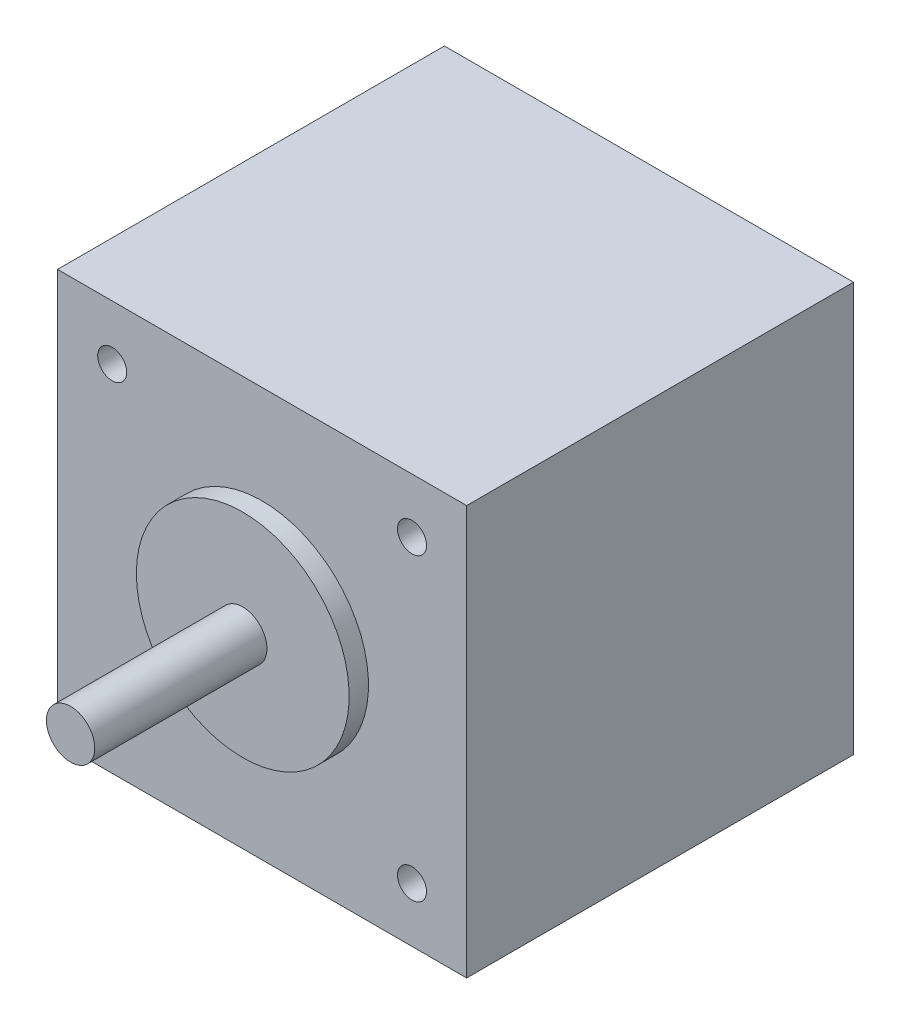
SolidWorks part; units mm, degrees
ref_plane "Спереди" through (0, 0, 0) normal (0, 0, 1) x (1, 0, 0)
ref_plane "Сверху" through (0, 0, 0) normal (0, 1, 0) x (1, 0, 0)
ref_plane "Справа" through (0, 0, 0) normal (1, 0, 0) x (0, 0, -1)
other "Configuration Table"
sketch "Эскиз1" plane through (0, 0, 0) normal (0, 0, 1) x (1, 0, 0)
  line L1 (-21.15, -21.15) -> (21.15, -21.15)
  line L2 (-21.15, -21.15) -> (-21.15, 21.15)
  line L3 (-21.15, 21.15) -> (21.15, 21.15)
  line L4 (21.15, -21.15) -> (21.15, 21.15)
  line L5 (-21.15, -21.15) -> (21.15, 21.15) construction
  line L6 (-21.15, 21.15) -> (21.15, -21.15) construction
  point P0 (0, 0)
  dimension "D1" = 42.3
  dimension "D2" = 42.3
extrude "Корпус" add sketch "Эскиз1" along normal blind 40
sketch "Эскиз2" plane through (0, 0, 0) normal (0, 0, 1) x (1, 0, 0)
  circle A0 centre (0, 0) radius 2.5
extrude "Вал_ПРЕДВ" add sketch "Эскиз2" along normal blind 59.8
sketch "Эскиз3" plane through (0, 0, 0) normal (0, 0, 1) x (1, 0, 0)
  circle A0 centre (0, 0) radius 11
  dimension "D1" = 22
extrude "Буртик_ПРЕДВ" add sketch "Эскиз3" along normal blind 42
sketch "Эскиз4" plane through (0, 0, 0) normal (0, 0, 1) x (1, 0, 0)
  circle A0 centre (0, 0) radius 8
  dimension "D1" = 16
sketch "Эскиз5" plane through (0, 0, 0) normal (0, 0, 1) x (1, 0, 0)
  circle A0 centre (-15.5, -15.5) radius 1.5
  circle A1 centre (-15.5, 15.5) radius 1.5
  circle A2 centre (15.5, -15.5) radius 1.5
  circle A3 centre (15.5, 15.5) radius 1.5
  dimension "D1" = 3
  dimension "D2" = 3
  dimension "D3" = 3
  dimension "D4" = 3
extrude "Крепеж_М3_ПРЕДВ" cut sketch "Эскиз5" against normal blind 4.5 from offset 40
equation "\"Мотор X ширина корпуса\"= 42.3"
equation "\"Мотор X высота корпуса\"= 42.3"
equation "\"Мотор X длина корпуса\"= 40"
equation "\"Мотор X вылет вала\"= 19.8"
equation "\"Мотор Y ширина корпуса\"= 42.3"
equation "\"Мотор Y высота корпуса\"= 42.3"
equation "\"Мотор Y длина корпуса\"= 48"
equation "\"Мотор Y вылет вала\"= 30"
equation "\"Мотор Z ширина корпуса\"= 42"
equation "\"Мотор Z высота корпуса\"= 42"
equation "\"Мотор Z длина корпуса\"= 40"
equation "\"Мотор Z вылет вала\"= 23"
equation "\"Мотор диаметр вала ПРЕДВ\"= 5"
equation "\"Мотор шаг крепления ПРЕДВ\"= 31"
equation "\"Мотор диаметр отверстий ПРЕДВ\"= 3"
equation "\"Мотор глубина отверстий ПРЕДВ\"= 4.5"
equation "\"Мотор диаметр буртика ПРЕДВ\"= 22"
equation "\"Мотор высота буртика ПРЕДВ\"= 2"
equation "\"Мотор диаметр шкива ПРЕДВ\"= 16"
equation "\"Мотор длина шкива ПРЕДВ\"= 12"
equation "\"Мотор отступ шкива ПРЕДВ\"= 5"
equation "\"Мотор X шаг градусов\"= 1.8"
equation "\"Мотор Y шаг градусов\"= 1.8"
equation "\"Мотор Z шаг градусов\"= 1.8"
equation "\"Мотор Y диаметр ротора\"= 25.78"
equation "\"D1@Эскиз1\" = \"Мотор X ширина корпуса\""
equation "\"D1@Корпус\" = \"Мотор X длина корпуса\""
equation "\"D1@Эскиз2\" = \"Мотор диаметр вала ПРЕДВ\""
equation "\"D1@Вал_ПРЕДВ\" = \"Мотор X длина корпуса\" + \"Мотор X вылет вала\""
equation "\"D1@Эскиз3\" = \"Мотор диаметр буртика ПРЕДВ\""
equation "\"D1@Буртик_ПРЕДВ\" = \"Мотор X длина корпуса\" + \"Мотор высота буртика ПРЕДВ\""
equation "\"D1@Эскиз4\" = \"Мотор диаметр шкива ПРЕДВ\""
equation "\"D1@Эскиз5\" = \"Мотор диаметр отверстий ПРЕДВ\""
equation "\"D2@Эскиз5\" = \"Мотор диаметр отверстий ПРЕДВ\""
equation "\"D3@Эскиз5\" = \"Мотор диаметр отверстий ПРЕДВ\""
equation "\"D4@Эскиз5\" = \"Мотор диаметр отверстий ПРЕДВ\""
equation "\"D1@Крепеж_М3_ПРЕДВ\" = \"Мотор глубина отверстий ПРЕДВ\""
equation "\"D19@Крепеж_М3_ПРЕДВ\" = \"Мотор X длина корпуса\""
equation "\"Ширина груза\"= 420"
equation "\"Глубина груза\"= 490"
equation "\"Высота груза\"= 297"
equation "\"Ширина ячейки\"= \"Ширина груза\" + 10"
equation "\"Глубина ячейки\"= \"Глубина груза\" + 10"
equation "\"Высота ячейки\"= \"Высота груза\" + 10 + 13"
equation "\"Колво ячеек ширина\"= 2"
equation "\"Колво ячеек высота\"= 2"
equation "\"Толщина стенки\" = 6"
equation "\"Крепление дверцы\"= 5"
equation "\"Ширина рейки\"= \"Толщина шестерни\""
equation "\"Высота рейки\"= 20"
equation "\"Высота пола\"= 20"
equation "\"Колво полозьев\"= 5"
equation "\"Отступ рейки\"= 20"
equation "\"Глубина каретки\"= \"Глубина ячейки\" + 30 + \"Мотор Y высота корпуса\" + 20"
equation "\"Отступ шпильки\"= 26"
equation "\"Диаметр шпильки\"= 5"
equation "\"Длинна шпильки\"= ( \"Высота ячейки\" + \"Толщина стенки\" + \"Высота пола\" ) * \"Колво ячеек высота\" + ( \"Толщина стенки\" + \"Отступ рейки\" ) * 2 "
equation "\"Ширина пластины\"= 50  "
equation "\"Высота зона выгрузки\"= \"Высота ячейки\" * 2 + \"Толщина стенки\" * 2"
equation "\"Колво выгрузки\"= 1"
equation "\"Отступ крепления мотора фиксации\" = 30"
equation "\"Диаметр оси\"= 10"
equation "\"Диаметр ролика\"= 20"
equation "\"Колво роликов\"= 10"
equation "\"Шаг роликов\"= \"Диаметр ролика\" + 20"
equation "\"Ширина ячейки выгрузки\"= \"Ширина ячейки\" + \"Толщина стенки\" + \"Отступ крепления мотора фиксации\"*2"
equation "\"Длинна рейки\"= ( \"Ширина ячейки\" + \"Толщина стенки\" + \"Крепление дверцы\" ) * \"Колво ячеек ширина\" + \"Ширина ячейки выгрузки\" * \"Колво выгрузки\" + \"Толщина стенки\""
equation "\"Толщина шестерни\"= 10"
